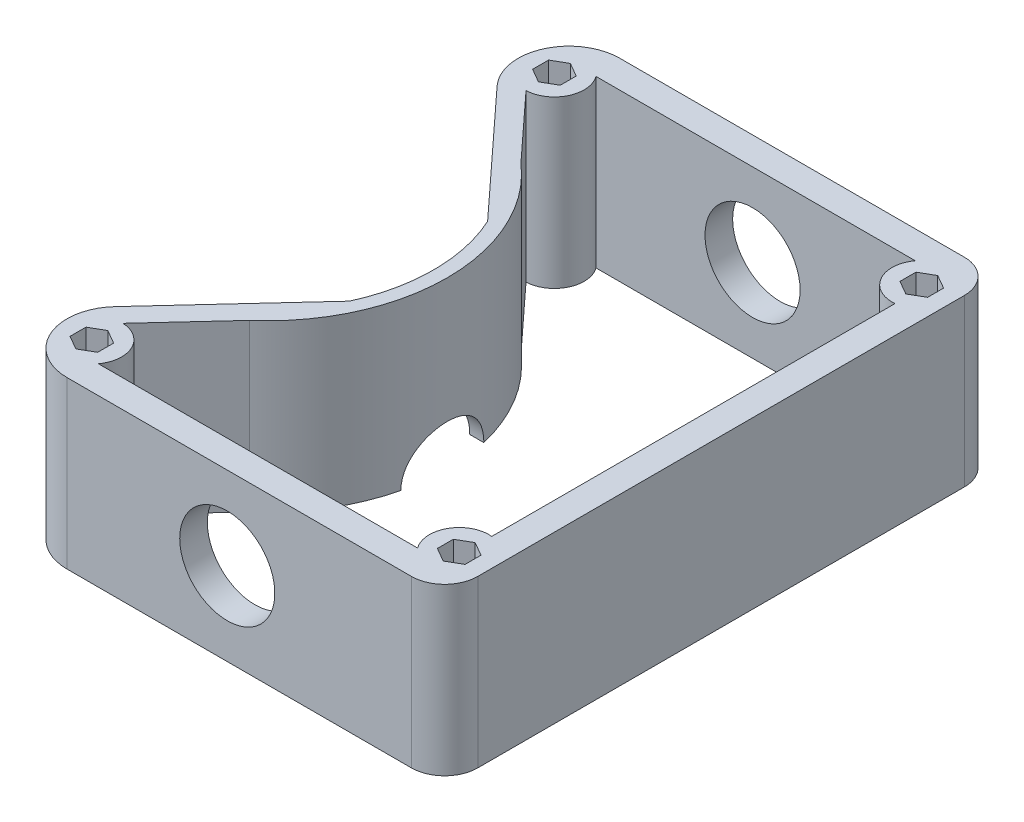
SolidWorks part; units mm, degrees
material "TPU"
ref_plane "Front Plane" through (0, 0, 0) normal (0, 0, 1) x (1, 0, 0)
ref_plane "Top Plane" through (0, 0, 0) normal (0, 1, 0) x (1, 0, 0)
ref_plane "Right Plane" through (0, 0, 0) normal (1, 0, 0) x (0, 0, -1)
sketch "Sketch1" plane through (0, 0, 0) normal (0, 1, 0) x (1, 0, 0)
  line L0 (66.675, 17.145) -> (66.675, 128.905) construction
  line L1 (-28.575, 9.525) -> (66.675, 9.525)
  line L2 (-28.575, 9.525) -> (-28.575, 15.875)
  line L3 (-28.575, 15.875) -> (66.675, 15.875)
  line L4 (66.675, 9.525) -> (66.675, 15.875)
  line L5 (-28.575, 9.525) -> (66.675, 15.875) construction
  line L6 (-28.575, 15.875) -> (66.675, 9.525) construction
  line L9 (-28.575, 9.525) -> (59.055, 9.525) construction
  point P0 (19.05, 12.7)
  point P15 (19.05, 9.525)
  dimension "D1" = 95.25
  dimension "D2" = 6.35
extrude "Boss-Extrude1" add sketch "Sketch1" along normal blind 38.1
sketch "Sketch2" plane through (0, 38.1, 0) normal (0, 1, 0) x (1, 0, 0)
  line L1 (60.325, 9.525) -> (66.675, 9.525)
  line L2 (60.325, 9.525) -> (60.325, 136.525)
  line L3 (60.325, 136.525) -> (66.675, 136.525)
  line L4 (66.675, 9.525) -> (66.675, 136.525)
  line L6 (32.8756, 15.875) -> (32.8756, 130.175) construction
  line L7 (-20.4, 15.875) -> (58.5, 15.875) construction
  line L8 (58.5, 130.175) -> (-20.4, 130.175) construction
  dimension "D1" = 127
  dimension "D2" = 6.35
extrude "Boss-Extrude2" add sketch "Sketch2" against normal up to surface (38.1 mm away) up to face at (19.05, 0, -12.7)
sketch "Sketch3" plane through (0, 38.1, 0) normal (0, 1, 0) x (1, 0, 0)
  line L0 (-28.575, 15.875) -> (-28.575, 9.525) construction
  line L1 (60.325, 136.525) -> (-28.575, 136.525)
  line L2 (60.325, 136.525) -> (60.325, 130.175)
  line L3 (60.325, 130.175) -> (-28.575, 130.175)
  line L4 (-28.575, 136.525) -> (-28.575, 130.175)
extrude "Boss-Extrude3" add sketch "Sketch3" against normal up to surface (38.1 mm away) up to face at (32.8083, 0, -53.975)
fillet "Fillet1" radius 7.62 2 edges at (66.675, 19.05, -9.525) (66.675, 19.05, -136.525)
sketch "Sketch10" plane through (0, 38.1, 0) normal (0, 1, 0) x (1, 0, 0)
  line L0 (-28.575, 9.525) -> (59.055, 9.525) construction
  line L2 (-28.575, 15.875) -> (-28.575, 9.525)
  line L5 (66.675, 73.025) -> (-141.5874, 73.025) construction
  line L7 (-28.575, 136.525) -> (-31.75, 136.525)
  line L11 (-31.75, 25.781) -> (-2.821, 57.15)
  line L15 (-28.575, 15.875) -> (-28.575, 22.225)
  line L16 (-28.575, 22.225) -> (-10.4944, 41.8306)
  line L17 (-28.575, 123.825) -> (-10.4944, 104.2194)
  line L18 (-31.75, 120.269) -> (-2.821, 88.9)
  line L19 (-10.4944, 41.8306) -> (-2.821, 57.15) construction
  line L22 (-28.575, 136.525) -> (-28.575, 123.825)
  line L26 (-31.75, 136.525) -> (-31.75, 120.269)
  line L27 (-31.75, 25.781) -> (-31.75, 9.525)
  line L28 (-31.75, 9.525) -> (-28.575, 9.525)
  line L29 (66.675, 17.145) -> (66.675, 128.905) construction
  arc A0 (-2.821, 57.15) -> (-2.821, 88.9) centre (-37.4562, 73.025) ccw
  arc A2 (-10.4944, 104.2194) -> (-10.4944, 41.8306) centre (-37.4562, 73.025) cw
  dimension "D7" = 31.75
  dimension "D6" = 38.1
  dimension "D1" = 16.256
  dimension "D2" = 3.175
  dimension "D3" = 12.7
  dimension "D4" = 42.672
  dimension "D5" = 26.67
extrude "Boss-Extrude4" add sketch "Sketch10" against normal up to surface (38.1 mm away) up to face at (26.0966, 0, -73.025)
sketch "Sketch12" plane through (60.325, 0, 0) normal (-1, 0, 0) x (0, 0, 1)
  line L0 (-88.9, 0) -> (-82.55, 0) construction
  line L1 (-88.9, 0) -> (-57.15, 0) construction
  line L2 (-57.15, 0) -> (-63.5, 0) construction
  line L3 (-82.55, 0) -> (-63.5, 0)
  arc A0 (-82.55, 0) -> (-63.5, 0) centre (-73.025, 0) cw
  dimension "D1" = 19.05
extrude "Cut-Extrude8" cut sketch "Sketch12" along normal up to surface (92.075 mm away) up to face at (-31.75, 19.05, -128.397)
fillet "Fillet2" 2 edges at (-31.75, 19.05, -120.269) (-31.75, 19.05, -136.525) type full round first side face at (-17.2855, 19.05, -104.5845) second side face at (13.6525, 19.05, -136.525) middle face at (-31.75, 19.05, -128.397)
fillet "Fillet3" 2 edges at (-31.75, 19.05, -25.781) (-31.75, 19.05, -9.525) type full round first side face at (-17.2855, 19.05, -41.4655) second side face at (13.6525, 19.05, -9.525) middle face at (-31.75, 19.05, -17.653)
fillet "Fillet4" radius 6.35 2 edges at (60.325, 19.05, -130.175) (60.325, 19.05, -15.875)
sketch "Sketch15" plane through (0, 38.1, 0) normal (0, 1, 0) x (1, 0, 0)
  line L0 (0.6438, 73.025) -> (66.675, 73.025) construction
  line L1 (66.675, 17.145) -> (66.675, 128.905) construction
  line L2 (-24.7273, 23.5658) -> (-24.7273, 26.7408) construction
  line L3 (-21.5523, 21.7327) -> (-24.7273, 23.5658)
  line L4 (-24.7273, 23.5658) -> (-27.9023, 21.7327)
  line L5 (-27.9023, 21.7327) -> (-27.9023, 18.0665)
  line L6 (-27.9023, 18.0665) -> (-24.7273, 16.2334)
  line L7 (-24.7273, 16.2334) -> (-21.5523, 18.0665)
  line L8 (-21.5523, 18.0665) -> (-21.5523, 21.7327)
  line L9 (-30.7676, 16.5233) -> (63.5, 69.215) construction
  line L10 (63.5, 69.215) -> (63.5, 9.525) construction
  line L11 (59.6523, 129.8166) -> (56.4773, 127.9835)
  line L12 (59.055, 9.525) -> (63.5, 9.525) construction
  line L13 (60.325, 69.215) -> (66.675, 69.215) construction
  line L14 (60.325, 123.825) -> (60.325, 22.225) construction
  line L15 (-21.5523, 127.9835) -> (-21.5523, 124.3173)
  line L16 (-24.7273, 129.8166) -> (-21.5523, 127.9835)
  line L17 (-27.9023, 127.9835) -> (-24.7273, 129.8166)
  line L18 (-27.9023, 124.3173) -> (-27.9023, 127.9835)
  line L19 (-24.7273, 122.4842) -> (-27.9023, 124.3173)
  line L20 (-21.5523, 124.3173) -> (-24.7273, 122.4842)
  line L21 (17.4625, 120.6024) -> (17.4625, 25.4476) construction
  line L22 (62.8273, 127.9835) -> (59.6523, 129.8166)
  line L23 (62.8273, 124.3173) -> (62.8273, 127.9835)
  line L24 (-31.75, 124.8361) -> (-31.75, 21.2139) construction
  line L25 (-31.75, 73.025) -> (66.675, 73.025) construction
  line L26 (59.6523, 122.4842) -> (62.8273, 124.3173)
  line L27 (56.4773, 124.3173) -> (59.6523, 122.4842)
  line L28 (56.4773, 127.9835) -> (56.4773, 124.3173)
  line L29 (56.4773, 18.0665) -> (56.4773, 21.7327)
  line L30 (59.6523, 16.2334) -> (56.4773, 18.0665)
  line L31 (62.8273, 18.0665) -> (59.6523, 16.2334)
  line L32 (62.8273, 21.7327) -> (62.8273, 18.0665)
  line L33 (59.6523, 23.5658) -> (62.8273, 21.7327)
  line L34 (56.4773, 21.7327) -> (59.6523, 23.5658)
  arc A2 (-26.3148, 17.15) -> (-23.1398, 17.15) centre (-24.7273, 19.8996) ccw construction
  circle A3 centre (59.6523, 126.1504) radius 6.8412
  arc A4 (-2.821, 57.15) -> (-2.821, 88.9) centre (-37.4562, 73.025) ccw construction
  circle A7 centre (-24.7273, 19.8996) radius 6.8412
  arc A8 (-28.6538, 29.1383) -> (-20.0611, 9.525) centre (-20.0611, 21.2139) ccw construction
  circle A9 centre (-24.7273, 19.8996) radius 3.175 construction
  circle A10 centre (-24.7273, 126.1504) radius 6.8412
  arc A11 (-20.0611, 136.525) -> (-28.6538, 116.9117) centre (-20.0611, 124.8361) ccw construction
  circle A12 centre (59.6523, 19.8996) radius 6.8412
  point P49 (17.4625, 73.025)
  line M11 (60.325, 123.825) -> (60.325, 22.225)
  arc M12 (60.325, 22.225) -> (53.975, 15.875) centre (53.975, 22.225) cw
  line M13 (53.975, 15.875) -> (-28.575, 15.875)
  line M15 (-28.575, 22.225) -> (-10.4944, 41.8306)
  line M17 (-10.4944, 104.2194) -> (-28.575, 123.825)
  line M19 (-28.575, 130.175) -> (53.975, 130.175)
  arc M20 (53.975, 130.175) -> (60.325, 123.825) centre (53.975, 123.825) cw
  dimension "D1" = 3.175
  dimension "D2" = 3.81
extrude "Boss-Extrude7" add sketch "Sketch15" against normal up to surface (38.1 mm away) contours A7 L8 L7 L6 L5 L4 L3 M15 M13 | A7 L3 L8 M13 M15 | A12 L29 L34 L33 M13 M12 M11 | A12 L33 L32 L31 L30 L29 M11 M12 M13 | A3 L28 L11 L22 L23 L26 M11 M19 M20 | A3 L26 L27 L28 M19 M11 M20 | A10 L20 L19 L18 L17 L16 L15 M17 M19 | A10 L15 L20 M19 M17 region at (58.6883, 38.1, -129.4728) region at (56.0673, 38.1, -124.3501) region at (-30.7182, 38.1, -17.0187) region at (64.5854, 38.1, -24.3693) region at (56.0673, 38.1, -21.6999) region at (-18.4056, 38.1, -128.2066) up to face at (10.1062, 0, -73.025)
sketch "Sketch21" plane through (0, 38.1, 0) normal (0, 1, 0) x (1, 0, 0)
  line L0 (60.325, 119.3424) -> (60.325, 26.7076) construction
  line L1 (-21.5523, 21.7327) -> (-24.7273, 23.5658)
  line L2 (-24.7273, 23.5658) -> (-27.9023, 21.7327)
  line L3 (-27.9023, 21.7327) -> (-27.9023, 18.0665)
  line L4 (-27.9023, 18.0665) -> (-24.7273, 16.2334)
  line L5 (-24.7273, 16.2334) -> (-21.5523, 18.0665)
  line L6 (-21.5523, 18.0665) -> (-21.5523, 21.7327)
  line L7 (3.7752, 73.025) -> (60.325, 73.025) construction
  line L9 (17.4625, 120.6024) -> (17.4625, 25.4476) construction
  line L10 (56.4773, 18.0665) -> (56.4773, 21.7327)
  line L11 (59.6523, 16.2334) -> (56.4773, 18.0665)
  line L12 (62.8273, 18.0665) -> (59.6523, 16.2334)
  line L13 (62.8273, 21.7327) -> (62.8273, 18.0665)
  line L14 (59.6523, 23.5658) -> (62.8273, 21.7327)
  line L15 (56.4773, 21.7327) -> (59.6523, 23.5658)
  line L16 (59.6523, 129.8166) -> (56.4773, 127.9835)
  line L17 (62.8273, 127.9835) -> (59.6523, 129.8166)
  line L18 (62.8273, 124.3173) -> (62.8273, 127.9835)
  line L19 (59.6523, 122.4842) -> (62.8273, 124.3173)
  line L20 (56.4773, 124.3173) -> (59.6523, 122.4842)
  line L21 (56.4773, 127.9835) -> (56.4773, 124.3173)
  line L22 (-21.5523, 127.9835) -> (-21.5523, 124.3173)
  line L23 (-24.7273, 129.8166) -> (-21.5523, 127.9835)
  line L24 (-27.9023, 127.9835) -> (-24.7273, 129.8166)
  line L25 (-27.9023, 124.3173) -> (-27.9023, 127.9835)
  line L26 (-24.7273, 122.4842) -> (-27.9023, 124.3173)
  line L27 (-21.5523, 124.3173) -> (-24.7273, 122.4842)
  circle A0 centre (-24.7273, 19.8996) radius 3.175 construction
  arc A1 (-10.4944, 41.8306) -> (-10.4944, 104.2194) centre (-37.4562, 73.025) ccw construction
extrude "Cut-Extrude12" cut sketch "Sketch21" against normal through all
sketch "Sketch4" plane through (0, 0, -136.525) normal (0, 0, -1) x (-1, 0, 0)
  line L0 (-16.7569, 19.05) -> (-16.7569, 29.972) construction
  line L1 (-66.675, 19.05) -> (-2.6599, 19.05) construction
  line L2 (-66.675, 0) -> (-66.675, 38.1) construction
  line L3 (20.0611, 0) -> (20.0611, 38.1) construction
  line L4 (-16.7569, 19.05) -> (-5.8349, 19.05) construction
  line L5 (20.0611, 19.05) -> (-2.6599, 19.05) construction
  circle A0 centre (-16.7569, 19.05) radius 10.922
  dimension "D1" = 21.844
  dimension "D2" = 10.922
  dimension "D3" = 3.175
extrude "Cut-Extrude1" cut sketch "Sketch4" against normal through all contours A0 region at (16.7569, 19.05, -136.525)
sketch "Sketch22" plane through (0, 0, -136.525) normal (0, 0, -1) x (-1, 0, 0)
  line L0 (-5.8349, 19.05) -> (-27.6789, 19.05) construction
  line L1 (-16.7569, 8.128) -> (-16.7569, 29.972) construction
  circle A0 centre (-16.7569, 19.05) radius 10.922 construction
  circle A1 centre (-16.7569, 19.05) radius 6.2304 construction
